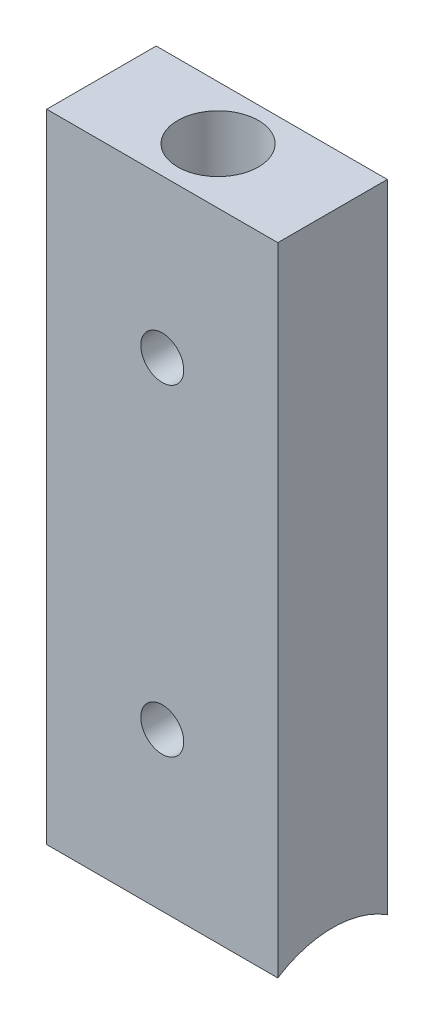
SolidWorks part; units mm, degrees
ref_plane "Front" through (0, 0, 0) normal (0, 0, 1) x (1, 0, 0)
ref_plane "Top" through (0, 0, 0) normal (0, 1, 0) x (1, 0, 0)
ref_plane "Right" through (0, 0, 0) normal (1, 0, 0) x (0, 0, -1)
sketch "Sketch1" plane through (0, 0, 0) normal (0, 0, 1) x (1, 0, 0)
  line L1 (-10.765, 29.665) -> (10.765, 29.665)
  line L2 (-10.765, 29.665) -> (-10.765, -29.665)
  line L3 (-10.765, -29.665) -> (10.765, -29.665)
  line L4 (10.765, 29.665) -> (10.765, -29.665)
  line L5 (-10.765, 29.665) -> (10.765, -29.665) construction
  line L6 (-10.765, -29.665) -> (10.765, 29.665) construction
  point P0 (0, 0)
  dimension "D1" = 21.53
  dimension "D2" = 59.33
extrude "Boss-Extrude1" add sketch "Sketch1" along normal blind 10.2
sketch "Sketch2" plane through (0, 29.665, 0) normal (0, 1, 0) x (1, 0, 0)
  line L0 (0, -55) -> (0, 55) construction
  circle A0 centre (0, -5) radius 3.76
  dimension "D1" = 7.52
extrude "Cut-Extrude1" cut sketch "Sketch2" against normal blind 10
sketch "Sketch3" plane through (10.765, 0, 0) normal (1, 0, 0) x (0, 0, -1)
  line L0 (0, 55) -> (0, -55) construction
  line L1 (-10.2, -29.665) -> (0, -29.665) construction
  line L2 (-10.2, -29.665) -> (0, -29.665)
  arc A0 (-10.2, -29.665) -> (0, -29.665) centre (-5.1, -37.5567) cw
extrude "Cut-Extrude2" cut sketch "Sketch3" against normal up to next
sketch "Sketch4" plane through (0, 0, 10.2) normal (0, 0, 1) x (1, 0, 0)
  line L0 (0, -55) -> (0, 55) construction
  line L1 (55, 0) -> (-55, 0) construction
  circle A0 centre (0, 15) radius 2
  circle A2 centre (0, -15) radius 2
  dimension "D1" = 4
  dimension "D2" = 15
extrude "Cut-Extrude3" cut sketch "Sketch4" against normal up to next
